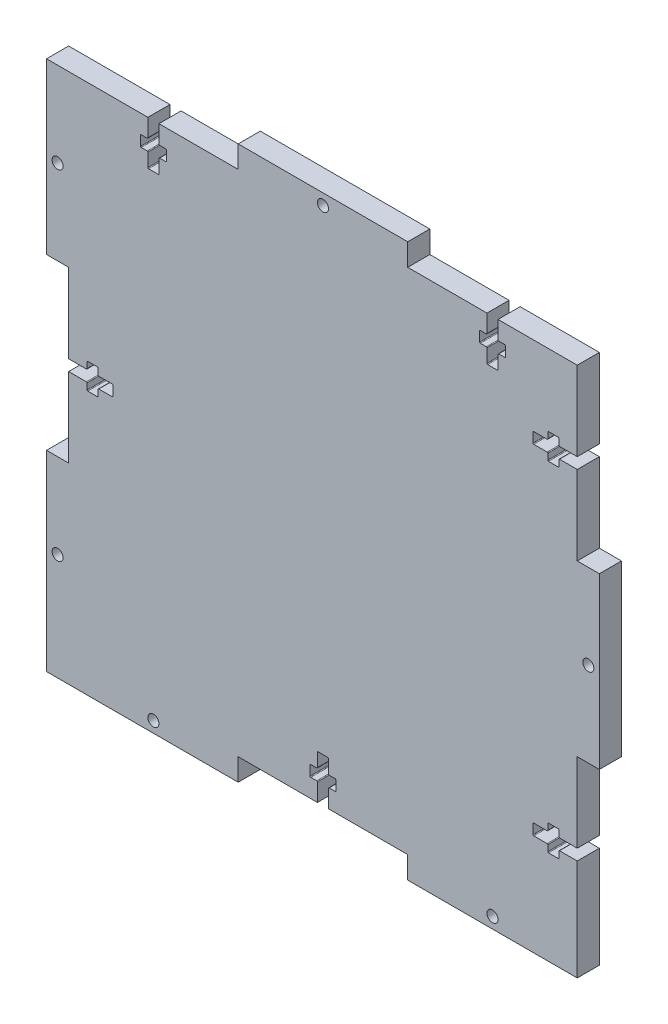
SolidWorks part; units mm, degrees
ref_plane "Front Plane" through (0, 0, 0) normal (0, 0, 1) x (1, 0, 0)
ref_plane "Top Plane" through (0, 0, 0) normal (0, 1, 0) x (1, 0, 0)
ref_plane "Right Plane" through (0, 0, 0) normal (1, 0, 0) x (0, 0, -1)
sketch "Sketch1" plane through (0, 0, 0) normal (0, 0, 1) x (1, 0, 0)
  line L0 (-69, 69) -> (-23, 69)
  line L5 (-75, -75) -> (75, -75) construction
  line L6 (-75, -75) -> (-75, 75) construction
  line L7 (-75, 75) -> (75, 75) construction
  line L8 (75, -75) -> (75, 75) construction
  line L9 (75, 23) -> (69, 23)
  line L10 (69, -23) -> (75, -23)
  line L11 (-69, -69) -> (69, -69) construction
  line L12 (-69, -69) -> (-69, 69) construction
  line L13 (-69, 69) -> (69, 69) construction
  line L14 (69, -69) -> (69, 69) construction
  line L15 (-69, -69) -> (69, 69) construction
  line L16 (69, -69) -> (69, -23)
  line L17 (-23, 69) -> (-23, 75)
  line L18 (-23, 75) -> (23, 75)
  line L19 (23, 75) -> (23, 69)
  line L20 (23, 69) -> (69, 69)
  line L21 (75, -23) -> (75, 23)
  line L22 (69, 23) -> (69, 69)
  line L23 (-75, 23) -> (-69, 23)
  line L24 (-69, 69) -> (-75, 69)
  line L25 (-75, 69) -> (-75, 23)
  line L26 (69, -69) -> (69, -75)
  line L27 (69, -75) -> (23, -75)
  line L28 (23, -75) -> (23, -69)
  line L29 (23, -69) -> (-23, -69)
  line L30 (-23, -69) -> (-23, -75)
  line L31 (-23, -75) -> (-69, -75)
  line L32 (-69, -75) -> (-69, -69) construction
  line L33 (-69, 23) -> (-69, -23)
  line L34 (-69, -23) -> (-75, -23)
  line L35 (-75, -23) -> (-75, -69)
  line L36 (-75, -69) -> (-69, -69) construction
  line L37 (-46, 69) -> (-46, -75) construction
  line L38 (-69, 69) -> (69, -69) construction
  line L39 (-75, -75) -> (-69, -75)
  line L40 (-75, -75) -> (-75, -69)
  point P0 (0, 0)
  point P6 (-7, -7)
  point P26 (0, -75)
  point P27 (-75, 0)
  dimension "D1" = 150
  dimension "D2" = 150
  dimension "D5" = 46
  dimension "D3" = 6
  dimension "D6" = 6
  dimension "D7" = 6
extrude "Box Side" add sketch "Sketch1" along normal blind 6
sketch "Sketch2" plane through (0, 0, 6) normal (0, 0, 1) x (1, 0, 0)
  line L0 (23, 72) -> (-23, 72) construction
  line L1 (23, 75) -> (23, 69) construction
  line L2 (-23, 69) -> (-23, 75) construction
  line L3 (-46, 69) -> (-46, -75) construction
  line L5 (0, 75) -> (0, 69) construction
  line L6 (-23, 75) -> (23, 75) construction
  line L7 (-69, 69) -> (69, 69) construction
  line L16 (-46, 69) -> (-46, -75) construction
  line L21 (0, -69) -> (0, 69) construction
  line L35 (-69, 69) -> (-23, 69) construction
  line L36 (-44.5, 69) -> (-44.5, 64.2)
  line L37 (-44.3, 64) -> (-42.7, 64)
  line L38 (-42.5, 63.8) -> (-42.5, 61.2)
  line L39 (-42.7, 61) -> (-44.3, 61)
  line L40 (-44.5, 60.8) -> (-44.5, 57.2)
  line L46 (-44.7, 57) -> (-47.3, 57)
  line L48 (-44.5, 69) -> (-47.5, 69)
  line L51 (-47.5, 60.8) -> (-47.5, 57.2)
  line L52 (-49.3, 61) -> (-47.7, 61)
  line L53 (-49.5, 63.8) -> (-49.5, 61.2)
  line L54 (-47.7, 64) -> (-49.3, 64)
  line L55 (-47.5, 69) -> (-47.5, 64.2)
  line L56 (47.5, 69) -> (47.5, 64.2)
  line L57 (47.7, 64) -> (49.3, 64)
  line L58 (49.5, 63.8) -> (49.5, 61.2)
  line L59 (49.3, 61) -> (47.7, 61)
  line L60 (47.5, 60.8) -> (47.5, 57.2)
  line L61 (44.5, 69) -> (47.5, 69)
  line L62 (44.7, 57) -> (47.3, 57)
  line L63 (44.5, 60.8) -> (44.5, 57.2)
  line L64 (42.7, 61) -> (44.3, 61)
  line L65 (42.5, 63.8) -> (42.5, 61.2)
  line L66 (44.3, 64) -> (42.7, 64)
  line L67 (44.5, 69) -> (44.5, 64.2)
  line L68 (-69, -69) -> (69, 69) construction
  line L69 (-69, -69) -> (69, 69) construction
  line L70 (75, 0) -> (69, 0) construction
  line L71 (72, 23) -> (72, -23) construction
  line L72 (69, 44.5) -> (64.2, 44.5)
  line L73 (64, 44.3) -> (64, 42.7)
  line L74 (63.8, 42.5) -> (61.2, 42.5)
  line L75 (61, 42.7) -> (61, 44.3)
  line L76 (60.8, 44.5) -> (57.2, 44.5)
  line L77 (57, 44.7) -> (57, 47.3)
  line L78 (69, 44.5) -> (69, 47.5)
  line L79 (60.8, 47.5) -> (57.2, 47.5)
  line L80 (61, 49.3) -> (61, 47.7)
  line L81 (63.8, 49.5) -> (61.2, 49.5)
  line L82 (64, 47.7) -> (64, 49.3)
  line L83 (69, 47.5) -> (64.2, 47.5)
  line L84 (69, -47.5) -> (64.2, -47.5)
  line L85 (64, -47.7) -> (64, -49.3)
  line L86 (63.8, -49.5) -> (61.2, -49.5)
  line L87 (61, -49.3) -> (61, -47.7)
  line L88 (60.8, -47.5) -> (57.2, -47.5)
  line L89 (69, -44.5) -> (69, -47.5)
  line L90 (57, -44.7) -> (57, -47.3)
  line L91 (60.8, -44.5) -> (57.2, -44.5)
  line L92 (61, -42.7) -> (61, -44.3)
  line L93 (63.8, -42.5) -> (61.2, -42.5)
  line L94 (64, -44.3) -> (64, -42.7)
  line L95 (69, -44.5) -> (64.2, -44.5)
  line L120 (-69, 69) -> (69, -69) construction
  line L121 (-69, 69) -> (69, -69) construction
  line L122 (-1.5, -69) -> (1.5, -69)
  line L123 (-23, -69) -> (23, -69) construction
  line L124 (1.5, -69) -> (1.5, -64.2)
  line L125 (1.7, -64) -> (3.3, -64)
  line L126 (3.5, -63.8) -> (3.5, -61.2)
  line L127 (3.3, -61) -> (1.7, -61)
  line L128 (1.5, -60.8) -> (1.5, -57.2)
  line L129 (1.3, -57) -> (-1.3, -57)
  line L130 (-1.5, -60.8) -> (-1.5, -57.2)
  line L131 (-3.3, -61) -> (-1.7, -61)
  line L132 (-3.5, -63.8) -> (-3.5, -61.2)
  line L133 (-1.7, -64) -> (-3.3, -64)
  line L134 (-1.5, -69) -> (-1.5, -64.2)
  line L135 (-69, -1.5) -> (-64.2, -1.5)
  line L136 (-64, -1.7) -> (-64, -3.3)
  line L137 (-63.8, -3.5) -> (-61.2, -3.5)
  line L138 (-61, -3.3) -> (-61, -1.7)
  line L139 (-60.8, -1.5) -> (-57.2, -1.5)
  line L140 (-57, 1.3) -> (-57, -1.3)
  line L141 (-60.8, 1.5) -> (-57.2, 1.5)
  line L142 (-61, 3.3) -> (-61, 1.7)
  line L143 (-63.8, 3.5) -> (-61.2, 3.5)
  line L144 (-64, 1.7) -> (-64, 3.3)
  line L145 (-69, 1.5) -> (-64.2, 1.5)
  line L146 (-69, -1.5) -> (-69, 1.5)
  line L147 (-69, -72) -> (-23, -72) construction
  line L148 (-23, 69) -> (-75, 69) construction
  line L149 (-23, -75) -> (-23, -69) construction
  line L150 (-69, -69) -> (-69, -75) construction
  line L151 (-75, -75) -> (-23, -75) construction
  circle A0 centre (0, 72) radius 1.5
  arc A1 (-44.5, 57.2) -> (-44.7, 57) centre (-44.7, 57.2) cw
  arc A2 (-44.3, 61) -> (-44.5, 60.8) centre (-44.3, 60.8) ccw
  arc A3 (-42.5, 61.2) -> (-42.7, 61) centre (-42.7, 61.2) cw
  arc A4 (-42.7, 64) -> (-42.5, 63.8) centre (-42.7, 63.8) cw
  arc A5 (-44.5, 64.2) -> (-44.3, 64) centre (-44.3, 64.2) ccw
  arc A6 (-47.5, 64.2) -> (-47.7, 64) centre (-47.7, 64.2) cw
  arc A7 (-49.3, 64) -> (-49.5, 63.8) centre (-49.3, 63.8) ccw
  arc A8 (-49.5, 61.2) -> (-49.3, 61) centre (-49.3, 61.2) ccw
  arc A9 (-47.7, 61) -> (-47.5, 60.8) centre (-47.7, 60.8) cw
  arc A10 (-47.5, 57.2) -> (-47.3, 57) centre (-47.3, 57.2) ccw
  arc A11 (47.5, 57.2) -> (47.3, 57) centre (47.3, 57.2) cw
  arc A12 (47.7, 61) -> (47.5, 60.8) centre (47.7, 60.8) ccw
  arc A13 (49.5, 61.2) -> (49.3, 61) centre (49.3, 61.2) cw
  arc A14 (49.3, 64) -> (49.5, 63.8) centre (49.3, 63.8) cw
  arc A15 (47.5, 64.2) -> (47.7, 64) centre (47.7, 64.2) ccw
  arc A16 (44.5, 64.2) -> (44.3, 64) centre (44.3, 64.2) cw
  arc A17 (42.7, 64) -> (42.5, 63.8) centre (42.7, 63.8) ccw
  arc A18 (42.5, 61.2) -> (42.7, 61) centre (42.7, 61.2) ccw
  arc A19 (44.3, 61) -> (44.5, 60.8) centre (44.3, 60.8) cw
  arc A20 (44.5, 57.2) -> (44.7, 57) centre (44.7, 57.2) ccw
  arc A21 (57.2, 44.5) -> (57, 44.7) centre (57.2, 44.7) cw
  arc A22 (61, 44.3) -> (60.8, 44.5) centre (60.8, 44.3) ccw
  arc A23 (61.2, 42.5) -> (61, 42.7) centre (61.2, 42.7) cw
  arc A24 (64, 42.7) -> (63.8, 42.5) centre (63.8, 42.7) cw
  arc A25 (64.2, 44.5) -> (64, 44.3) centre (64.2, 44.3) ccw
  arc A26 (64.2, 47.5) -> (64, 47.7) centre (64.2, 47.7) cw
  arc A27 (64, 49.3) -> (63.8, 49.5) centre (63.8, 49.3) ccw
  arc A28 (61.2, 49.5) -> (61, 49.3) centre (61.2, 49.3) ccw
  arc A29 (61, 47.7) -> (60.8, 47.5) centre (60.8, 47.7) cw
  arc A30 (57.2, 47.5) -> (57, 47.3) centre (57.2, 47.3) ccw
  arc A31 (57.2, -47.5) -> (57, -47.3) centre (57.2, -47.3) cw
  arc A32 (61, -47.7) -> (60.8, -47.5) centre (60.8, -47.7) ccw
  arc A33 (61.2, -49.5) -> (61, -49.3) centre (61.2, -49.3) cw
  arc A34 (64, -49.3) -> (63.8, -49.5) centre (63.8, -49.3) cw
  arc A35 (64.2, -47.5) -> (64, -47.7) centre (64.2, -47.7) ccw
  arc A36 (64.2, -44.5) -> (64, -44.3) centre (64.2, -44.3) cw
  arc A37 (64, -42.7) -> (63.8, -42.5) centre (63.8, -42.7) ccw
  arc A38 (61.2, -42.5) -> (61, -42.7) centre (61.2, -42.7) ccw
  arc A39 (61, -44.3) -> (60.8, -44.5) centre (60.8, -44.3) cw
  arc A40 (57.2, -44.5) -> (57, -44.7) centre (57.2, -44.7) ccw
  circle A41 centre (72, 0) radius 1.5
  arc A62 (1.5, -57.2) -> (1.3, -57) centre (1.3, -57.2) ccw
  arc A63 (1.7, -61) -> (1.5, -60.8) centre (1.7, -60.8) cw
  arc A64 (3.5, -61.2) -> (3.3, -61) centre (3.3, -61.2) ccw
  arc A65 (3.3, -64) -> (3.5, -63.8) centre (3.3, -63.8) ccw
  arc A66 (1.5, -64.2) -> (1.7, -64) centre (1.7, -64.2) cw
  arc A67 (-1.5, -64.2) -> (-1.7, -64) centre (-1.7, -64.2) ccw
  arc A68 (-3.3, -64) -> (-3.5, -63.8) centre (-3.3, -63.8) cw
  arc A69 (-3.5, -61.2) -> (-3.3, -61) centre (-3.3, -61.2) cw
  arc A70 (-1.7, -61) -> (-1.5, -60.8) centre (-1.7, -60.8) ccw
  arc A71 (-1.5, -57.2) -> (-1.3, -57) centre (-1.3, -57.2) cw
  arc A72 (-57.2, -1.5) -> (-57, -1.3) centre (-57.2, -1.3) ccw
  arc A73 (-61, -1.7) -> (-60.8, -1.5) centre (-60.8, -1.7) cw
  arc A74 (-61.2, -3.5) -> (-61, -3.3) centre (-61.2, -3.3) ccw
  arc A75 (-64, -3.3) -> (-63.8, -3.5) centre (-63.8, -3.3) ccw
  arc A76 (-64.2, -1.5) -> (-64, -1.7) centre (-64.2, -1.7) cw
  arc A77 (-64.2, 1.5) -> (-64, 1.7) centre (-64.2, 1.7) ccw
  arc A78 (-64, 3.3) -> (-63.8, 3.5) centre (-63.8, 3.3) cw
  arc A79 (-61.2, 3.5) -> (-61, 3.3) centre (-61.2, 3.3) cw
  arc A80 (-61, 1.7) -> (-60.8, 1.5) centre (-60.8, 1.7) ccw
  arc A81 (-57.2, 1.5) -> (-57, 1.3) centre (-57.2, 1.3) cw
  circle A82 centre (-46, -72) radius 1.5
  circle A83 centre (46, -72) radius 1.5
  circle A84 centre (-72, 46) radius 1.5
  circle A85 centre (-72, -46) radius 1.5
  point P6 (0, 72)
  point P38 (0, 0)
  point P56 (-46, 57)
  point P88 (46, 57)
  point P161 (57, 46)
  point P162 (57, -46)
  point P198 (0, -57)
  point P231 (-57, 0)
  point P234 (-42.5, 62.5)
  dimension "D1" = 3
  dimension "D2" = 0.2
  dimension "D8" = 0.2
  dimension "D14" = 3
  dimension "D4" = 3
  dimension "D7" = 1.5
  dimension "D10" = 3
  dimension "D12" = 1.5
  dimension "D9" = 12
  dimension "D11" = 5
  dimension "D13" = 7
  dimension "D3" = 12
  dimension "D5" = 7
  dimension "D6" = 5
extrude "Screw Cut-outs" cut sketch "Sketch2" against normal through all
equation "\"filletRadius\"=0.2"
equation "\"D8@Sketch2\"=\"filletRadius\""
equation "\"D2@Sketch2\"=\"filletRadius\""
equation "\"fingerWidth\"= 46"
equation "\"D5@Sketch1\"=\"fingerWidth\""
equation "\"wallThickness\"= 6"
equation "\"D3@Sketch1\" = \"wallThickness\""
equation "\"D6@Sketch1\" = \"wallThickness\""
equation "\"D7@Sketch1\" = \"wallThickness\""
equation "\"D1@Box Side\" = \"wallThickness\""
equation "\"M3\"= 3"
equation "\"D14@Sketch2\"=\"M3\""
equation "\"D1@Sketch2\"=\"M3\""
equation "\"D12@Sketch2\"=\"M3\"/2"
equation "\"nutThickness\"=3"
equation "\"D10@Sketch2\" = \"nutThickness\""
equation "\"boltLength\"= 12"
equation "\"D9@Sketch2\" = \"boltLength\""
equation "\"distanceToNut\"= 5"
equation "\"D11@Sketch2\" = \"distanceToNut\""
equation "\"D13@Sketch2\" = \"nutWidth\""
equation "\"D7@Sketch2\"=\"M3\"/2"
equation "\"D4@Sketch2\" = \"nutThickness\""
equation "\"D3@Sketch2\" = \"boltLength\""
equation "\"D5@Sketch2\" = \"nutWidth\""
equation "\"D6@Sketch2\" = \"distanceToNut\""
equation "\"sideLength\"=150"
equation "\"D1@Sketch1\"=\"sideLength\""
equation "\"D2@Sketch1\"=\"sideLength\""
equation "\"nutWidth\"=7"
